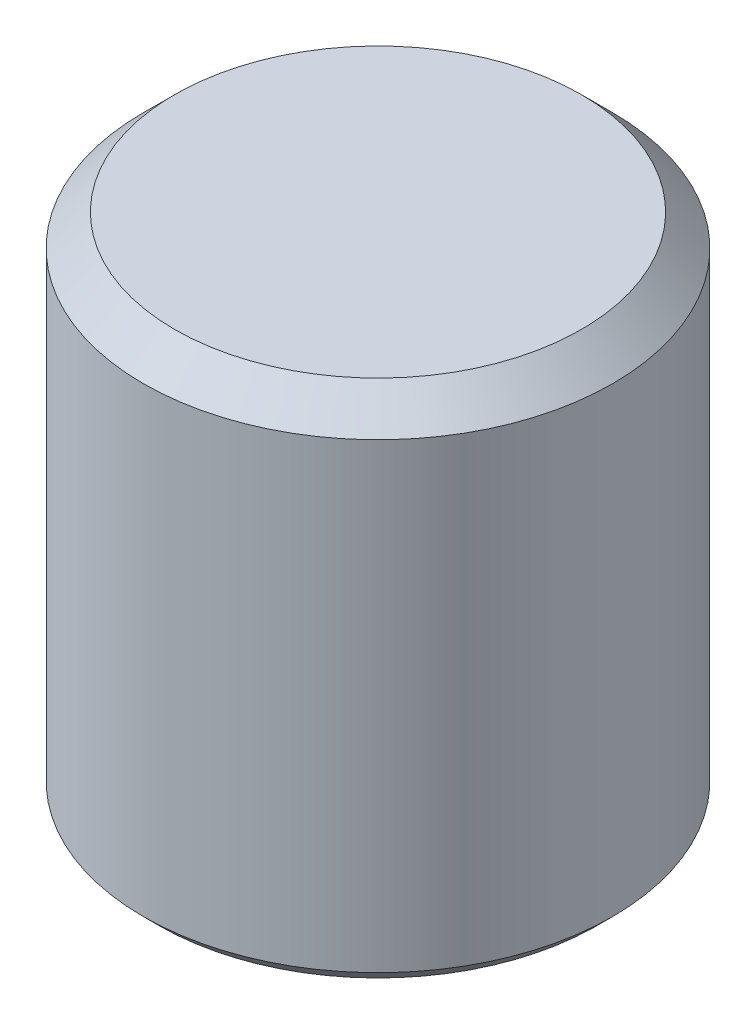
SolidWorks part; units mm, degrees
material "Malleable Cast Iron"
ref_plane "Front Plane" through (0, 0, 0) normal (0, 0, 1) x (1, 0, 0)
ref_plane "Top Plane" through (0, 0, 0) normal (0, 1, 0) x (1, 0, 0)
ref_plane "Right Plane" through (0, 0, 0) normal (1, 0, 0) x (0, 0, -1)
sketch "Sketch1" plane through (0, 0, 0) normal (0, 1, 0) x (1, 0, 0)
  circle A0 centre (0, 0) radius 6
  dimension "D1" = 12
extrude "Boss-Extrude1" add sketch "Sketch1" along normal blind 13
sketch "Sketch2" plane through (0, 0, 0) normal (0, -1, 0) x (1, 0, 0)
  circle A0 centre (0, 0) radius 5
  dimension "D1" = 10
extrude "Cut-Extrude1" cut sketch "Sketch2" against normal blind 10 contours A0
chamfer "Chamfer1" distance 0.8 angle 45 1 edges at (0, 13, 6)
chamfer "Chamfer2" distance 0.4 angle 45 2 edges at (0, 0, 6) (0, 0, -5)
